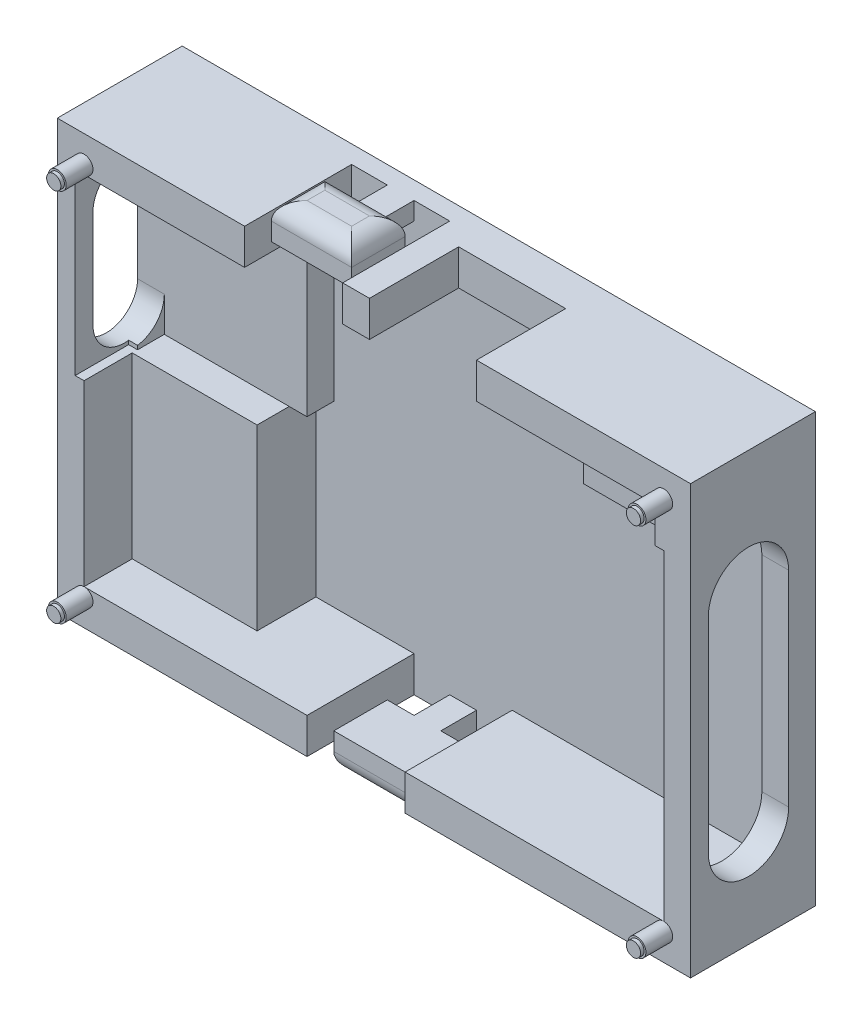
SolidWorks part; units mm, degrees
ref_plane "前视基准面" through (0, 0, 0) normal (0, 0, 1) x (1, 0, 0)
ref_plane "上视基准面" through (0, 0, 0) normal (0, 1, 0) x (1, 0, 0)
ref_plane "右视基准面" through (0, 0, 0) normal (1, 0, 0) x (0, 0, -1)
sketch "草图1" plane through (0, 0, 0) normal (0, 0, 1) x (1, 0, 0)
  line L5 (-17.75, 12) -> (17.75, 12)
  line L6 (-17.75, 12) -> (-17.75, -12)
  line L7 (-17.75, -12) -> (17.75, -12)
  line L8 (17.75, 12) -> (17.75, -12)
  line L9 (-17.75, 12) -> (17.75, -12) construction
  line L10 (-17.75, -12) -> (17.75, 12) construction
  point P0 (0, 0)
  dimension "D1" = 35.5
  dimension "D2" = 24
extrude "凸台-拉伸1" add sketch "草图1" along normal blind 7
sketch "草图2" plane through (0, 0, 7) normal (0, 0, 1) x (1, 0, 0)
  line L5 (-16.25, 11) -> (16.75, -11) construction
  line L6 (-16.25, -11) -> (16.75, 11) construction
  line L9 (-17.75, 12) -> (-17.75, -12) construction
  line L10 (-16.25, 11) -> (16.75, 11)
  line L11 (-16.25, 11) -> (-16.25, -11)
  line L12 (-16.25, -11) -> (16.75, -11)
  line L13 (16.75, 11) -> (16.75, -11)
  line L15 (17.75, 12) -> (-17.75, 12) construction
  line L16 (17.75, -12) -> (17.75, 12) construction
  point P0 (0, 0)
  dimension "D1" = 1.5
  dimension "D2" = 1
  dimension "D3" = 1
  dimension "D4" = 22
extrude "切除-拉伸1" cut sketch "草图2" against normal blind 6
sketch "草图3" plane through (-17.75, 0, 0) normal (-1, 0, 0) x (0, 0, 1)
  line L0 (4.25, 7.45) -> (4.25, 1.95) construction
  line L1 (6, 7.45) -> (6, 1.95)
  line L2 (2.5, 7.45) -> (2.5, 1.95)
  line L3 (0, 12) -> (0, -12) construction
  line L4 (7, 12) -> (0, 12) construction
  arc A0 (6, 7.45) -> (2.5, 7.45) centre (4.25, 7.45) ccw
  arc A1 (2.5, 1.95) -> (6, 1.95) centre (4.25, 1.95) ccw
  point P2 (4.25, 4.7)
  dimension "D3" = 5.5
  dimension "D4" = 4.55
  dimension "D1" = 2.5
  dimension "D2" = 3.5
extrude "切除-拉伸2" cut sketch "草图3" against normal blind 2
sketch "草图6" plane through (0, 0, 1) normal (0, 0, 1) x (1, 0, 0)
  line L14 (-16.25, 10) -> (15.75, 10)
  line L15 (-16.25, 11) -> (-16.25, -11) construction
  line L16 (15.75, 10) -> (15.75, -10)
  line L17 (15.75, -10) -> (-16.25, -10)
  line L18 (-16.25, -10) -> (-16.25, -11)
  line L19 (-16.25, -11) -> (16.75, -11)
  line L20 (16.75, -11) -> (16.75, 11)
  line L21 (16.75, 11) -> (-16.25, 11)
  line L22 (-16.25, 11) -> (-16.25, 10)
  dimension "D1" = 1
  dimension "D2" = 1
  dimension "D3" = 1
extrude "凸台-拉伸2" add sketch "草图6" along normal blind 6
sketch "草图7" plane through (0, 0, 1) normal (0, 0, 1) x (1, 0, 0)
  line L23 (15.75, 10) -> (10.75, 10)
  line L24 (15.75, 10) -> (15.75, 8)
  line L25 (15.75, 8) -> (10.75, 8)
  line L26 (10.75, 10) -> (10.75, 8)
  dimension "D3" = 5
  dimension "D8" = 2
extrude "凸台-拉伸3" add sketch "草图7" along normal blind 5
sketch "草图10" plane through (15.75, 0, 0) normal (-1, 0, 0) x (0, 0, 1)
  line L0 (3.75, -6.45) -> (3.75, 5.05) construction
  line L1 (1.5, -6.45) -> (1.5, 5.05)
  line L2 (6, -6.45) -> (6, 5.05)
  line L4 (7, -12) -> (0, -12) construction
  line L5 (7, -12) -> (7, 12) construction
  arc A0 (1.5, -6.45) -> (6, -6.45) centre (3.75, -6.45) ccw
  arc A1 (6, 5.05) -> (1.5, 5.05) centre (3.75, 5.05) ccw
  point P2 (3.75, -0.7)
  point P7 (3.75, 7.3)
  point P8 (3.75, -8.7)
  dimension "D2" = 16
  dimension "D1" = 11.5
  dimension "D3" = 1
  dimension "D4" = 3.3
extrude "切除-拉伸4" cut sketch "草图10" against normal blind 2
sketch "草图12" plane through (0, 0, 7) normal (0, 0, 1) x (1, 0, 0)
  line L0 (-16.25, 10) -> (-16.25, -10) construction
  line L8 (15.75, -10) -> (-16.25, -10) construction
  line L9 (-3.75, -10) -> (1.75, -10)
  line L10 (-3.75, -10) -> (-3.75, -12)
  line L11 (-3.75, -12) -> (1.75, -12)
  line L12 (1.75, -10) -> (1.75, -12)
  line L15 (-16.25, 10) -> (-16.25, -10) construction
  dimension "D1" = 12.5
  dimension "D2" = 18
  dimension "D3" = 2
extrude "切除-拉伸6" cut sketch "草图12" against normal blind 6
sketch "草图19" plane through (0, 0, 1) normal (0, 0, 1) x (1, 0, 0)
  line L0 (-16.25, 10) -> (10.75, 10) construction
  line L1 (-16.25, 10) -> (-8.25, 10)
  line L2 (-16.25, 10) -> (-16.25, 0)
  line L3 (-16.25, 0) -> (-8.25, 0)
  line L4 (-8.25, 10) -> (-8.25, 0)
  dimension "D1" = 8
  dimension "D2" = 0
  dimension "D3" = 10
extrude "USB支撑" add sketch "草图19" along normal blind 1.5
sketch "草图25" plane through (0, 0, 7) normal (0, 0, 1) x (1, 0, 0)
  line L0 (1.75, -12) -> (17.75, -12) construction
  line L2 (15.75, 8) -> (16.25, 8)
  line L3 (15.75, 8) -> (15.75, -10)
  line L4 (15.75, -10) -> (16.25, -10)
  line L5 (16.25, 8) -> (16.25, -10)
  line L7 (-16.25, 10) -> (15.75, 10) construction
  line L8 (15.75, 10) -> (15.75, -10) construction
  dimension "D1" = 2
  dimension "D2" = 2
  dimension "D3" = 0
  dimension "D4" = 0.5
extrude "切除-拉伸12" cut sketch "草图25" against normal blind 6
sketch "草图26" plane through (0, 0, 7) normal (0, 0, 1) x (1, 0, 0)
  line L0 (17.75, 12) -> (-17.75, 12) construction
  line L1 (-17.75, 12) -> (-17.75, -12) construction
  line L2 (-17.75, -12) -> (-3.75, -12) construction
  circle A0 centre (-16.25, 10.5) radius 0.5
  circle A1 centre (-16.25, -10.5) radius 0.5
  dimension "D3" = 1
  dimension "D6" = 1
  dimension "D1" = 1.5
  dimension "D2" = 1.5
  dimension "D4" = 1.5
  dimension "D5" = 1.5
extrude "凸台-拉伸4" add sketch "草图26" along normal blind 1.5
sketch "草图27" plane through (0, 0, 7) normal (0, 0, 1) x (1, 0, 0)
  line L0 (17.75, -12) -> (17.75, 12) construction
  line L1 (17.75, 12) -> (-17.75, 12) construction
  line L2 (1.75, -12) -> (17.75, -12) construction
  circle A0 centre (16.25, 10.5) radius 0.5
  circle A1 centre (16.25, -10.5) radius 0.5
  dimension "D3" = 1
  dimension "D4" = 1.5
  dimension "D6" = 1
  dimension "D1" = 1.5
  dimension "D2" = 1.5
  dimension "D5" = 1.5
extrude "凸台-拉伸5" add sketch "草图27" along normal blind 1.5
sketch "草图28" plane through (0, 0, 7) normal (0, 0, 1) x (1, 0, 0)
  line L0 (-16.25, 10) -> (15.75, 10) construction
  line L1 (-7.25, 10) -> (-1.75, 10)
  line L2 (-7.25, 10) -> (-7.25, 12)
  line L3 (-7.25, 12) -> (-1.75, 12)
  line L4 (-1.75, 10) -> (-1.75, 12)
  line L5 (17.75, 12) -> (-17.75, 12) construction
  line L6 (-16.25, 10) -> (-16.25, 7.45) construction
  dimension "D1" = 9
  dimension "D2" = 5.5
extrude "切除-拉伸13" cut sketch "草图28" against normal blind 6
sketch "草图29" plane through (0, 0, 7) normal (0, 0, 1) x (1, 0, 0)
  line L1 (-0.25, 10) -> (5.75, 10)
  line L2 (-0.25, 10) -> (-0.25, 12)
  line L3 (-0.25, 12) -> (5.75, 12)
  line L4 (5.75, 10) -> (5.75, 12)
  line L5 (17.75, 12) -> (-1.75, 12) construction
  line L8 (-16.25, 10) -> (-16.25, -10) construction
  dimension "D1" = 16
  dimension "D2" = 6
extrude "切除-拉伸14" cut sketch "草图29" against normal blind 5
sketch "草图30" plane through (0, 0, 8.5) normal (0, 0, 1) x (1, 0, 0)
  circle A0 centre (-16.25, 10.5) radius 0.4
  dimension "D1" = 0.8
extrude "凸台-拉伸6" add sketch "草图30" along normal blind 0.2
sketch "草图31" plane through (0, 0, 8.5) normal (0, 0, 1) x (1, 0, 0)
  circle A0 centre (-16.25, -10.5) radius 0.4
  dimension "D1" = 0.8
extrude "凸台-拉伸7" add sketch "草图31" along normal blind 0.2
sketch "草图32" plane through (0, 0, 8.5) normal (0, 0, 1) x (1, 0, 0)
  circle A0 centre (16.25, 10.5) radius 0.4
  dimension "D1" = 0.8
extrude "凸台-拉伸8" add sketch "草图32" along normal blind 0.2
sketch "草图33" plane through (0, 0, 8.5) normal (0, 0, 1) x (1, 0, 0)
  circle A0 centre (16.25, -10.5) radius 0.4
  dimension "D1" = 0.8
extrude "凸台-拉伸9" add sketch "草图33" along normal blind 0.2
sketch "草图34" plane through (0, 0, 1) normal (0, 0, 1) x (1, 0, 0)
  line L0 (16.25, -10) -> (1.75, -10) construction
  line L1 (-16.25, 0) -> (-9.25, 0)
  line L2 (-16.25, 0) -> (-16.25, -10)
  line L3 (-16.25, -10) -> (-9.25, -10)
  line L4 (-9.25, 0) -> (-9.25, -10)
  dimension "D1" = 7
extrude "凸台-拉伸10" add sketch "草图34" along normal blind 3.3
sketch "草图35" plane through (0, 0, 7) normal (0, 0, 1) x (1, 0, 0)
  line L1 (-16.25, 10) -> (-16.75, 10)
  line L2 (-16.25, 10) -> (-16.25, 0)
  line L3 (-16.25, 0) -> (-16.75, 0)
  line L4 (-16.75, 10) -> (-16.75, 0)
  dimension "D1" = 0.5
  dimension "D2" = 10
extrude "切除-拉伸15" cut sketch "草图35" against normal blind 3
sketch "草图37" plane through (0, 0, 1) normal (0, 0, 1) x (1, 0, 0)
  line L0 (-3.75, -12) -> (1.75, -12) construction
  line L1 (-3.25, -12) -> (1.25, -12)
  line L2 (-3.25, -12) -> (-3.25, -10)
  line L3 (-3.25, -10) -> (1.25, -10)
  line L4 (1.25, -12) -> (1.25, -10)
  line L5 (1.75, -12) -> (1.75, -10) construction
  line L6 (-3.75, -10) -> (-3.75, -12) construction
  dimension "D1" = 0.5
  dimension "D2" = 0.5
  dimension "D3" = 2
extrude "凸台-拉伸12" add sketch "草图37" along normal blind 5
sketch "草图38" plane through (0, -12, 0) normal (0, -1, 0) x (1, 0, 0)
  line L1 (-3.25, 1) -> (-1.75, 1)
  line L2 (-3.25, 1) -> (-3.25, 3)
  line L3 (-3.25, 3) -> (-1.75, 3)
  line L4 (-1.75, 1) -> (-1.75, 3)
  line L5 (1.25, 1) -> (-0.25, 1)
  line L6 (1.25, 1) -> (1.25, 3)
  line L7 (1.25, 3) -> (-0.25, 3)
  line L8 (-0.25, 1) -> (-0.25, 3)
  dimension "D1" = 2
  dimension "D2" = 2
  dimension "D3" = 1.5
  dimension "D4" = 1.5
extrude "切除-拉伸16" cut sketch "草图38" against normal blind 2
sketch "草图39" plane through (0, 0, 6) normal (0, 0, 1) x (1, 0, 0)
  line L0 (1.25, -12) -> (1.25, -10) construction
  line L1 (-3.25, -10) -> (1.25, -10)
  line L2 (-3.25, -10) -> (-3.25, -11)
  line L3 (-3.25, -11) -> (1.25, -11)
  line L4 (1.25, -10) -> (1.25, -11)
  dimension "D1" = 1
extrude "切除-拉伸17" cut sketch "草图39" against normal blind 5
sketch "草图40" plane through (0, -12, 0) normal (0, -1, 0) x (1, 0, 0)
  line L0 (1.25, 6) -> (1.25, 3) construction
  line L1 (-3.25, 6) -> (1.25, 6)
  line L2 (-3.25, 6) -> (-3.25, 3)
  line L3 (-3.25, 3) -> (1.25, 3)
  line L4 (1.25, 6) -> (1.25, 3)
  line L6 (-3.25, 6) -> (1.25, 6) construction
  point P7 (0, 0)
  dimension "D1" = 3
  dimension "D2" = 0
extrude "凸台-拉伸13" add sketch "草图40" along normal blind 1
fillet "圆角2" radius 1 4 edges at (-1, -13, 3) (1.25, -13, 4.5) (-1, -13, 6) (-3.25, -13, 4.5)
sketch "草图41" plane through (0, 0, 1) normal (0, 0, 1) x (1, 0, 0)
  line L0 (-1.75, 12) -> (-7.25, 12) construction
  line L1 (-6.75, 12) -> (-2.25, 12)
  line L2 (-6.75, 12) -> (-6.75, 10)
  line L3 (-6.75, 10) -> (-2.25, 10)
  line L4 (-2.25, 12) -> (-2.25, 10)
  line L5 (-1.75, 10) -> (-1.75, 12) construction
  line L6 (-7.25, 12) -> (-7.25, 10) construction
  dimension "D1" = 0.5
  dimension "D2" = 0.5
  dimension "D3" = 2
extrude "凸台-拉伸14" add sketch "草图41" along normal blind 5
sketch "草图42" plane through (0, 12, 0) normal (0, 1, 0) x (1, 0, 0)
  line L1 (-6.75, -1) -> (-5.25, -1)
  line L2 (-6.75, -1) -> (-6.75, -3)
  line L3 (-6.75, -3) -> (-5.25, -3)
  line L4 (-5.25, -1) -> (-5.25, -3)
  line L5 (-2.25, -1) -> (-3.75, -1)
  line L6 (-2.25, -1) -> (-2.25, -3)
  line L7 (-2.25, -3) -> (-3.75, -3)
  line L8 (-3.75, -1) -> (-3.75, -3)
  dimension "D1" = 1.5
  dimension "D2" = 1.5
  dimension "D3" = 2
  dimension "D4" = 2
extrude "切除-拉伸18" cut sketch "草图42" against normal blind 2
sketch "草图43" plane through (0, 0, 6) normal (0, 0, 1) x (1, 0, 0)
  line L0 (-2.25, 10) -> (-2.25, 12) construction
  line L1 (-6.75, 10) -> (-2.25, 10)
  line L2 (-6.75, 10) -> (-6.75, 11)
  line L3 (-6.75, 11) -> (-2.25, 11)
  line L4 (-2.25, 10) -> (-2.25, 11)
extrude "切除-拉伸19" cut sketch "草图43" against normal blind 5
sketch "草图44" plane through (0, 12, 0) normal (0, 1, 0) x (1, 0, 0)
  line L0 (-2.25, -6) -> (-2.25, -3) construction
  line L1 (-6.75, -6) -> (-2.25, -6)
  line L2 (-6.75, -6) -> (-6.75, -3)
  line L3 (-6.75, -3) -> (-2.25, -3)
  line L4 (-2.25, -6) -> (-2.25, -3)
  dimension "D1" = 3
extrude "凸台-拉伸15" add sketch "草图44" along normal blind 1
fillet "圆角3" radius 1 4 edges at (-2.25, 13, 4.5) (-4.5, 13, 3) (-6.75, 13, 4.5) (-4.5, 13, 6)
